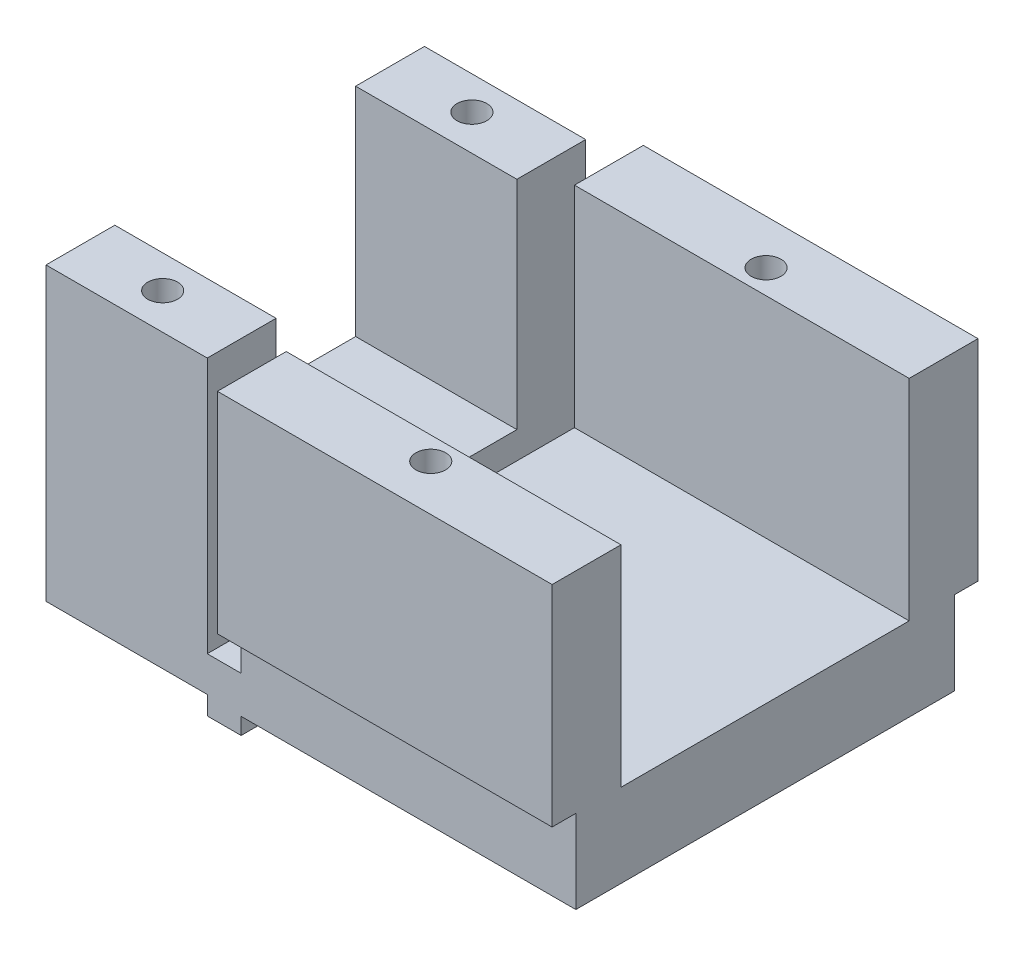
SolidWorks part; units mm, degrees
ref_plane "Front Plane" through (0, 0, 0) normal (0, 0, 1) x (1, 0, 0)
ref_plane "Top Plane" through (0, 0, 0) normal (0, 1, 0) x (1, 0, 0)
ref_plane "Right Plane" through (0, 0, 0) normal (1, 0, 0) x (0, 0, -1)
sketch "Sketch1" plane through (0, 0, 0) normal (0, 1, 0) x (1, 0, 0)
  line L0 (0, 16.5) -> (0, 17.135)
  line L5 (0, 0) -> (11.9, 0)
  line L6 (0, 0) -> (0, 16.5)
  line L7 (0, 16.5) -> (11.9, 16.5)
  line L8 (11.9, 0) -> (11.9, 16.5)
  line L9 (11.9, 16.5) -> (11.9, 17.135)
  line L10 (0, 17.135) -> (11.9, 17.135)
  line L11 (0, -0.635) -> (0, -5.715)
  line L12 (0, -5.715) -> (11.9, -5.715)
  line L13 (11.9, -5.715) -> (11.9, -0.635)
  line L14 (0, 0) -> (0, -0.635)
  line L15 (0, -0.635) -> (11.9, -0.635)
  line L16 (11.9, -0.635) -> (11.9, 0)
  line L17 (11.9, 17.135) -> (11.9, 22.215)
  line L18 (0, 17.135) -> (0, 22.215)
  line L19 (0, 22.215) -> (11.9, 22.215)
  dimension "D1" = 11.9
  dimension "D2" = 16.5
  dimension "D3" = 17.135
  dimension "D4" = 22.215
extrude "Boss-Extrude1" add sketch "Sketch1" along normal blind 1.27 contours L19 L18 L10 L17 | L5 L8 L7 L6 | L10 L0 L7 L9 | L15 L11 L12 L13 | L15 L16 L5 L14 region at (5.95, 0, -8.25) region at (5.95, 0, -16.8175) region at (5.95, 0, -19.675) region at (5.95, 0, 0.3175) region at (5.95, 0, 3.175)
extrude "Boss-Extrude2" add sketch "Sketch1<3>" along normal blind 16.77 contours L15 L11 L12 L13 | L19 L18 L10 L17 region at (5.95, 0, -19.675) region at (5.95, 0, 3.175)
sketch "Sketch1<3>" plane through (0, 0, 0) normal (0, 1, 0) x (1, 0, 0) same geometry as "Sketch1"
sketch "Sketch2" plane through (0, 16.77, 0) normal (0, 1, 0) x (1, 0, 0)
  line L0 (0, 17.135) -> (0, 22.215) construction
  line L1 (0, 22.215) -> (11.9, 22.215) construction
  circle A0 centre (5.95, 19.7654) radius 1.1
  dimension "D1" = 2.2
  dimension "D2" = 5.95
  dimension "D3" = 2.4496
extrude "Cut-Extrude1" cut sketch "Sketch2" against normal blind 10.16 contours A0
sketch "Sketch3" plane through (0, 16.77, 0) normal (0, 1, 0) x (1, 0, 0)
  line L0 (0, -0.635) -> (0, -5.715) construction
  line L1 (0, -0.635) -> (11.9, -0.635) construction
  circle A0 centre (5.95, -3.0563) radius 1.1
  dimension "D1" = 2.2
  dimension "D2" = 5.95
  dimension "D3" = 2.4213
extrude "Cut-Extrude2" cut sketch "Sketch3" against normal blind 10.16
sketch "Sketch4" plane through (11.9, 0, 0) normal (1, 0, 0) x (0, 0, -1)
  line L0 (-0.635, 1.27) -> (-0.635, -1.48)
  line L1 (-5.715, 0) -> (-5.715, -1.48)
  line L2 (-5.715, -1.48) -> (-0.635, -1.48)
  line L3 (22.215, 0) -> (22.215, -1.48)
  line L4 (22.215, -1.48) -> (-0.635, -1.48)
  line L5 (22.215, 16.77) -> (22.215, 0) construction
  line L6 (17.135, 16.77) -> (22.215, 16.77) construction
  line M9 (-5.715, 0) -> (22.215, 0)
  dimension "D1" = 18.25
extrude "Boss-Extrude4" add sketch "Sketch4" against normal blind 11.9 contours L4 L3 L0 M9 | L1 L2 L0 M9 region at (11.9, -0.74, -10.79) region at (11.9, -0.74, 3.175)
sketch "Sketch6" plane through (11.9, 0, 0) normal (1, 0, 0) x (0, 0, -1)
  line L0 (-0.635, 1.27) -> (-0.635, -1.48)
  line L1 (22.215, -1.48) -> (-5.715, -1.48) construction
  line L2 (-0.635, -1.48) -> (-0.635, -4.23)
  line L3 (-5.715, -1.48) -> (-5.715, -4.23)
  line L4 (-5.715, -4.23) -> (-0.635, -4.23)
  line L5 (22.215, -1.48) -> (22.215, -4.23)
  line L6 (22.215, -4.23) -> (-0.635, -4.23)
  line L7 (22.215, 16.77) -> (22.215, -1.48) construction
  line M9 (-5.715, -1.48) -> (22.215, -1.48)
extrude "Boss-Extrude5" add sketch "Sketch6" against normal blind 11.9 contours L6 L5 L2 M9 | L3 L4 L2 M9 region at (11.9, -2.855, -10.79) region at (11.9, -2.855, 3.175)
sketch "Sketch7" plane through (11.9, 0, 0) normal (1, 0, 0) x (0, 0, -1)
  line L0 (-0.635, 1.27) -> (-0.635, -2.855)
  line L1 (-0.635, -2.855) -> (-0.635, -4.23)
  line L2 (22.215, -4.23) -> (-5.715, -4.23) construction
  line L3 (-0.635, -2.855) -> (22.215, -2.855)
  line L4 (22.215, 16.77) -> (22.215, -4.23) construction
  line L5 (22.215, -2.855) -> (-5.715, -2.855)
  line L6 (-5.715, 16.77) -> (-5.715, -4.23) construction
  line L7 (-5.715, -2.855) -> (-5.715, -4.23)
  line L8 (-5.715, -4.23) -> (-0.635, -4.23)
  line L9 (22.215, -4.23) -> (22.215, -2.855)
  line L10 (-5.715, -4.23) -> (-5.715, -5.605)
  line L11 (-5.715, -5.605) -> (-0.635, -5.605)
  line L12 (-0.635, -5.605) -> (-0.635, -4.23)
  line L13 (-0.635, -5.605) -> (22.215, -5.605)
  line L14 (22.215, -5.605) -> (22.215, -4.23)
  line L15 (17.135, 16.77) -> (22.215, 16.77) construction
  line M1 (22.215, -4.23) -> (22.215, 16.77)
  line M7 (-5.715, 16.77) -> (-5.715, -4.23)
  line M8 (-5.715, -4.23) -> (22.215, -4.23)
  dimension "D1" = 19.625
extrude "Boss-Extrude6" add sketch "Sketch7" along normal blind 2.5 contours L1 L5 M7 M8 | L11 L12 L10 M8 | L3 L1 M8 M1 | L13 L14 L12 M8 region at (11.9, -3.5425, -10.79) region at (11.9, -3.5425, 3.175) region at (11.9, -4.9175, 3.175) region at (11.9, -4.9175, -10.79)
sketch "Sketch8" plane through (11.9, 0, 0) normal (1, 0, 0) x (0, 0, -1)
  line L0 (-0.635, 1.27) -> (-0.635, -1.63)
  line L1 (-0.635, -1.63) -> (-5.715, -1.63)
  line L2 (-5.715, 16.77) -> (-5.715, -2.855) construction
  line L3 (-5.715, -1.63) -> (-5.715, -2.855)
  line L4 (-5.715, -2.855) -> (22.215, -2.855)
  line L5 (22.215, -2.855) -> (-5.715, -2.855) construction
  line L6 (22.215, -2.855) -> (22.215, -1.63)
  line L7 (22.215, 16.77) -> (22.215, -2.855) construction
  line L8 (22.215, -1.63) -> (-0.635, -1.63)
  line L9 (17.135, 16.77) -> (22.215, 16.77) construction
  line M2 (-5.715, -2.855) -> (22.215, -2.855)
  line M3 (22.215, -2.855) -> (22.215, 16.77)
  line M9 (-5.715, 16.77) -> (-5.715, -2.855)
  dimension "D1" = 18.4
extrude "Boss-Extrude7" add sketch "Sketch8" along normal blind 2.5 contours L8 L1 M3 M9 M2 region at (11.9, -2.2425, -8.25)
sketch "Sketch19" plane through (0, 16.77, 0) normal (0, 1, 0) x (1, 0, 0)
  line L0 (0, 17.135) -> (0, 22.215) construction
  line L1 (0, 17.135) -> (11.9, 17.135)
  line L2 (0, 17.135) -> (0, 22.215)
  line L3 (0, 22.215) -> (11.9, 22.215)
  line L4 (11.9, 17.135) -> (11.9, 22.215)
  line L5 (0, -5.715) -> (11.9, -5.715)
  line L6 (0, -5.715) -> (0, -0.635)
  line L7 (0, -0.635) -> (11.9, -0.635)
  line L8 (11.9, -5.715) -> (11.9, -0.635)
  line L9 (0, 22.215) -> (11.9, 22.215) construction
  circle A0 centre (5.95, 19.7654) radius 1.1
  circle A1 centre (5.95, -3.0563) radius 1.1
  dimension "D1" = 2.2
  dimension "D2" = 25.2713
extrude "Boss-Extrude13" add sketch "Sketch19" along normal blind 0.5
sketch "Sketch20" plane through (14.4, 0, 0) normal (1, 0, 0) x (0, 0, -1)
  line L0 (-5.715, -1.63) -> (-5.715, -4.38)
  line L1 (-5.715, -1.63) -> (-5.715, -5.605) construction
  line L2 (-5.715, -1.63) -> (-5.715, 1.27)
  line L4 (-5.715, 17.27) -> (-5.715, -1.63) construction
  line L5 (-5.715, 1.27) -> (22.215, 1.27)
  line L6 (22.215, 17.27) -> (22.215, -1.63) construction
  line L7 (22.215, 1.27) -> (22.215, -3.6175)
  line L8 (22.215, -5.605) -> (22.215, -1.63) construction
  line L9 (22.215, -3.6175) -> (22.215, -4.38)
  line L10 (22.215, -4.38) -> (-5.715, -4.38)
  line L11 (-5.715, -5.605) -> (22.215, -5.605) construction
  dimension "D1" = 1.225
  dimension "D2" = 6.875
extrude "Boss-Extrude14" add sketch "Sketch20" along normal blind 24.7
sketch "Sketch21" plane through (0, 1.27, 0) normal (0, 1, 0) x (1, 0, 0)
  line L1 (14.4, -5.715) -> (39.1, -5.715)
  line L2 (14.4, -5.715) -> (14.4, 22.215)
  line L3 (14.4, 22.215) -> (39.1, 22.215)
  line L4 (39.1, -5.715) -> (39.1, 22.215)
extrude "Boss-Extrude16" add sketch "Sketch21" along normal blind 0.5
sketch "Sketch23" plane through (0, 1.77, 0) normal (0, 1, 0) x (1, 0, 0)
  line L0 (14.4, 8.25) -> (39.1, 8.25)
  line L1 (14.4, 22.215) -> (14.4, -5.715) construction
  line L2 (39.1, -5.715) -> (39.1, 22.215) construction
  line L3 (26.75, 8.25) -> (26.75, 18.25)
  line L4 (26.75, 8.25) -> (26.75, -1.75)
  line L6 (26.75, -1.75) -> (26.75, -2.385)
  line L7 (26.75, -2.385) -> (39.1, -2.385)
  line L8 (39.1, -2.385) -> (39.1, -7.465)
  line L9 (39.1, -7.465) -> (26.75, -7.465)
  line L10 (26.75, -7.465) -> (26.75, -2.385)
  line L11 (14.4, -2.385) -> (14.4, -7.465)
  line L12 (14.4, -7.465) -> (26.75, -7.465)
  line L13 (14.4, -2.385) -> (26.75, -2.385)
  line L14 (26.75, 18.25) -> (26.75, 18.885)
  line L15 (26.75, 18.885) -> (39.1, 18.885)
  line L16 (39.1, 18.885) -> (39.1, 23.965)
  line L17 (39.1, 23.965) -> (26.75, 23.965)
  line L18 (26.75, 23.965) -> (26.75, 18.885)
  line L19 (14.4, 18.885) -> (14.4, 23.965)
  line L20 (14.4, 23.965) -> (26.75, 23.965)
  line L21 (26.75, 18.885) -> (14.4, 18.885)
  line L22 (14.4, 22.215) -> (14.4, -5.715) construction
  line M6 (14.4, 22.215) -> (14.4, -5.715)
  line M7 (14.4, -5.715) -> (39.1, -5.715)
  line M8 (39.1, -5.715) -> (39.1, 22.215)
  line M9 (39.1, 22.215) -> (14.4, 22.215)
  dimension "D1" = 3.33
  dimension "D2" = 3.965
  dimension "D3" = 29.68
extrude "Boss-Extrude17" add sketch "Sketch23" along normal blind 15.5 contours L21 L18 M9 M6 | L20 L19 L18 M9 | L17 L18 L16 M9 | L18 L15 M9 M8 | L10 L7 M7 M8 | L10 L9 L8 M7 | L13 L10 M6 M7 | L11 L12 L10 M7 region at (20.575, 1.77, -20.55) region at (20.575, 1.77, 4.05) region at (20.575, 1.77, -23.09) region at (32.925, 1.77, -20.55) region at (20.575, 1.77, 6.59) region at (32.925, 1.77, 4.05) region at (32.925, 1.77, -23.09) region at (32.925, 1.77, 6.59)
sketch "Sketch24" plane through (0, 17.27, 0) normal (0, 1, 0) x (1, 0, 0)
  line L0 (26.75, 8.3552) -> (26.75, -4.0698)
  line L3 (39.1, 18.885) -> (39.1, 23.965) construction
  line L5 (39.1, 18.885) -> (14.4, 18.885) construction
  line L10 (26.75, 8.3552) -> (26.75, 20.675)
  circle A0 centre (26.75, 20.675) radius 1.1
  circle A1 centre (26.75, -4.0698) radius 1.1
  dimension "D1" = 2.2
  dimension "D2" = 12.35
  dimension "D3" = 1.79
  dimension "D4" = 10.5298
  dimension "D5" = 22.9548
extrude "Cut-Extrude3" cut sketch "Sketch24" against normal blind 10 contours A0 | A1 region at (27.5058, 17.27, 3.314) region at (25.9942, 17.27, -21.4308)
